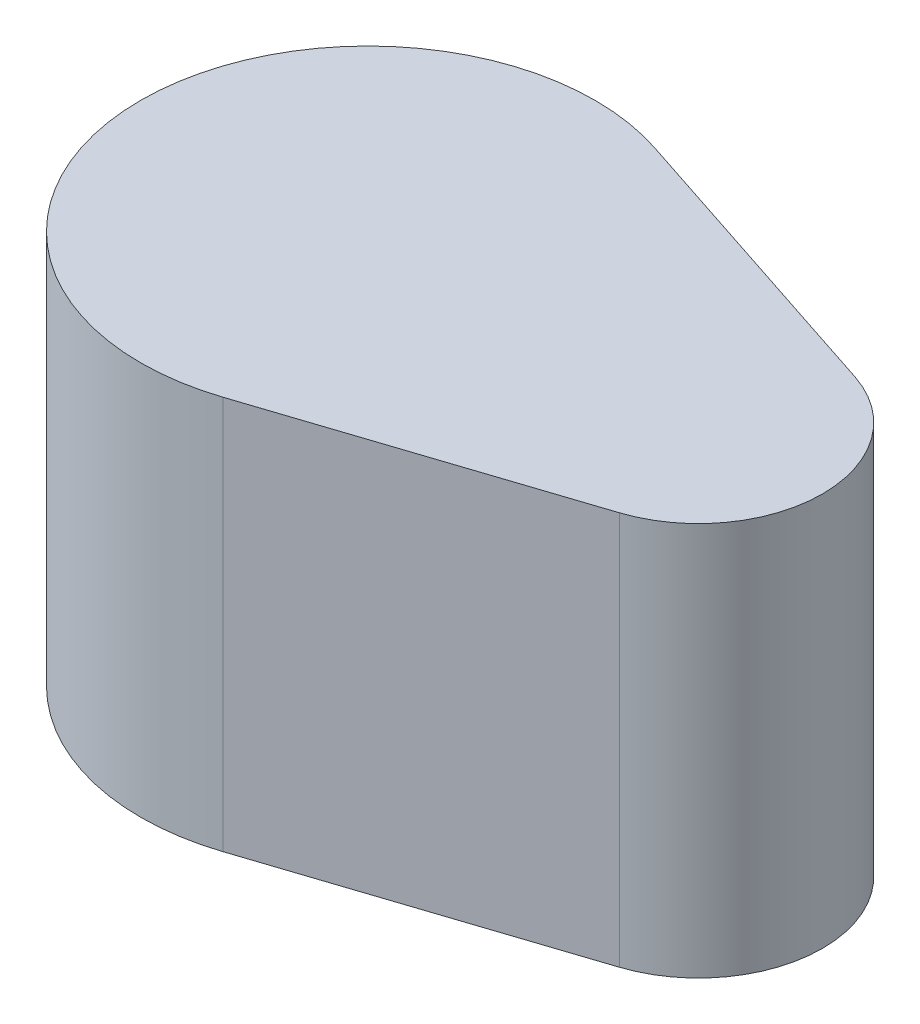
SolidWorks part; units mm, degrees
ref_plane "Front Plane" through (0, 0, 0) normal (0, 0, 1) x (1, 0, 0)
ref_plane "Top Plane" through (0, 0, 0) normal (0, 1, 0) x (1, 0, 0)
ref_plane "Right Plane" through (0, 0, 0) normal (1, 0, 0) x (0, 0, -1)
sketch "Sketch1" plane through (0, 0, 0) normal (0, 1, 0) x (1, 0, 0)
  line L0 (1.7188, 5.2245) -> (8.9375, 2.8498)
  line L1 (1.7188, -5.2245) -> (8.9375, -2.8498)
  line L3 (-5.5, 0) -> (-5.5, -16.5) construction
  line L4 (-5.5, -16.5) -> (11, -16.5) construction
  line L5 (11, -16.5) -> (11, 0) construction
  arc A0 (1.7188, 5.2245) -> (1.7188, -5.2245) centre (0, 0) ccw
  arc A1 (8.9375, -2.8498) -> (8.9375, 2.8498) centre (8, 0) ccw
  arc A2 (8.9375, -2.8498) -> (8.9375, 2.8498) centre (8, 0) ccw construction
  arc A3 (1.7188, 5.2245) -> (1.7188, -5.2245) centre (0, 0) ccw construction
  circle A5 centre (8, 0) radius 3 construction
  circle A7 centre (8, 0) radius 3 construction
  dimension "D1" = 5.5
  dimension "D2" = 3
  dimension "D3" = 16.5
extrude "Boss-Extrude1" add sketch "Sketch1" along normal blind 9.525
ref_axis "Axis1" through (0, 10.0012, 0) along (0, -1, 0)
